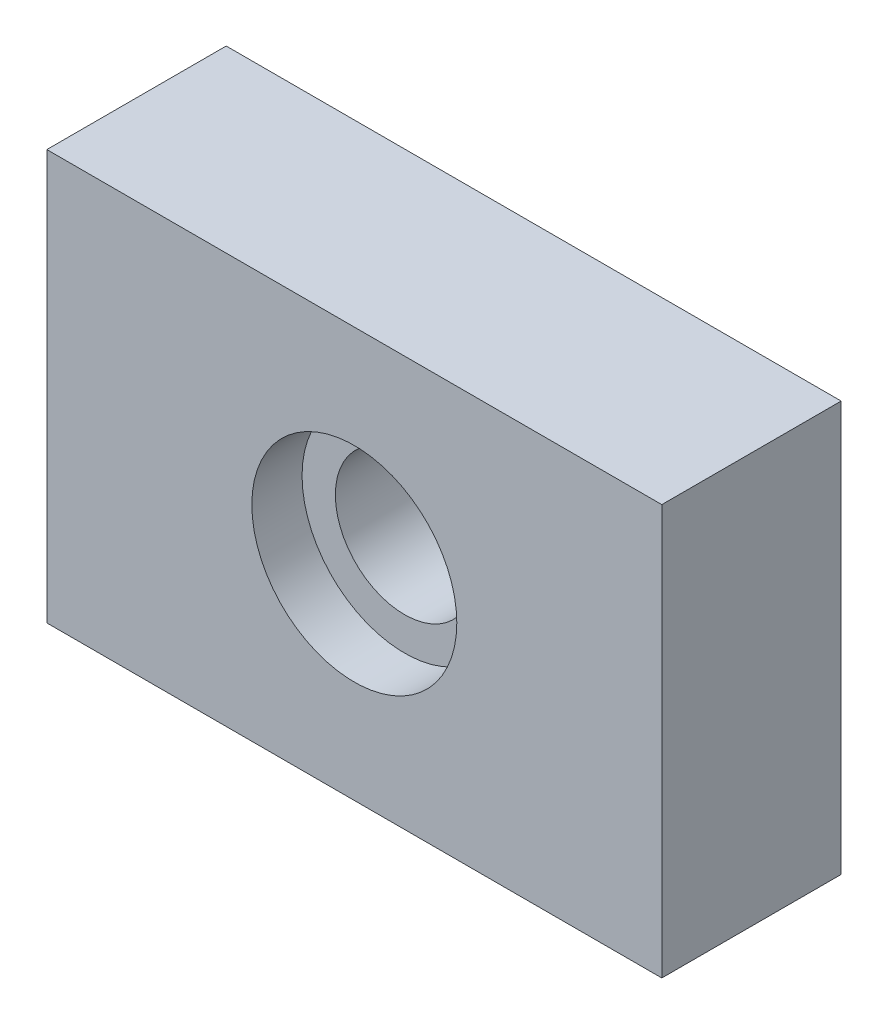
SolidWorks part; units mm, degrees
ref_plane "Front Plane" through (0, 0, 0) normal (0, 0, 1) x (1, 0, 0)
ref_plane "Top Plane" through (0, 0, 0) normal (0, 1, 0) x (1, 0, 0)
ref_plane "Right Plane" through (0, 0, 0) normal (1, 0, 0) x (0, 0, -1)
sketch "Sketch1" plane through (0, 0, 0) normal (0, 0, 1) x (1, 0, 0)
  line L1 (0, 0) -> (152.4, 0)
  line L2 (0, 0) -> (0, 101.6)
  line L3 (0, 101.6) -> (152.4, 101.6)
  line L4 (152.4, 0) -> (152.4, 101.6)
  dimension "D1" = 152.4
  dimension "D2" = 101.6
extrude "Boss-Extrude1" add sketch "Sketch1" along normal blind 44.45
sketch "Sketch2" plane through (0, 0, 0) normal (0, 0, -1) x (-1, 0, 0)
  line L0 (0, 50.8) -> (-152.4, 50.8) construction
  line L1 (0, 101.6) -> (0, 0) construction
  line L2 (-152.4, 0) -> (-152.4, 101.6) construction
  line L4 (-152.4, 101.6) -> (0, 101.6) construction
  line L5 (-76.2, 101.6) -> (-76.2, 0) construction
  line L6 (0, 0) -> (-152.4, 0) construction
  circle A0 centre (-76.2, 50.8) radius 25.4
  circle A1 centre (-76.2, 50.8) radius 17.145
  dimension "D1" = 50.8
  dimension "D2" = 34.29
extrude "Cut-Extrude1" cut sketch "Sketch2" against normal through all contours A1
extrude "Cut-Extrude3" cut sketch "Sketch2<2>" against normal blind 12.446
sketch "Sketch2<2>" plane through (0, 0, 0) normal (0, 0, -1) x (-1, 0, 0) same geometry as "Sketch2"
ref_plane "Plane2" through (0, 0, 22.225) normal (0, 0, -1) x (-1, 0, 0)
mirror "Mirror2" about plane through (0, 0, 22.225) normal (0, 0, -1) of "Cut-Extrude3"
equation "\"through_diamiter\"= 1.35"
equation "\"D2@Sketch2\"=\"through_diamiter\""
equation "\"bearing depth\"= 0.5"
